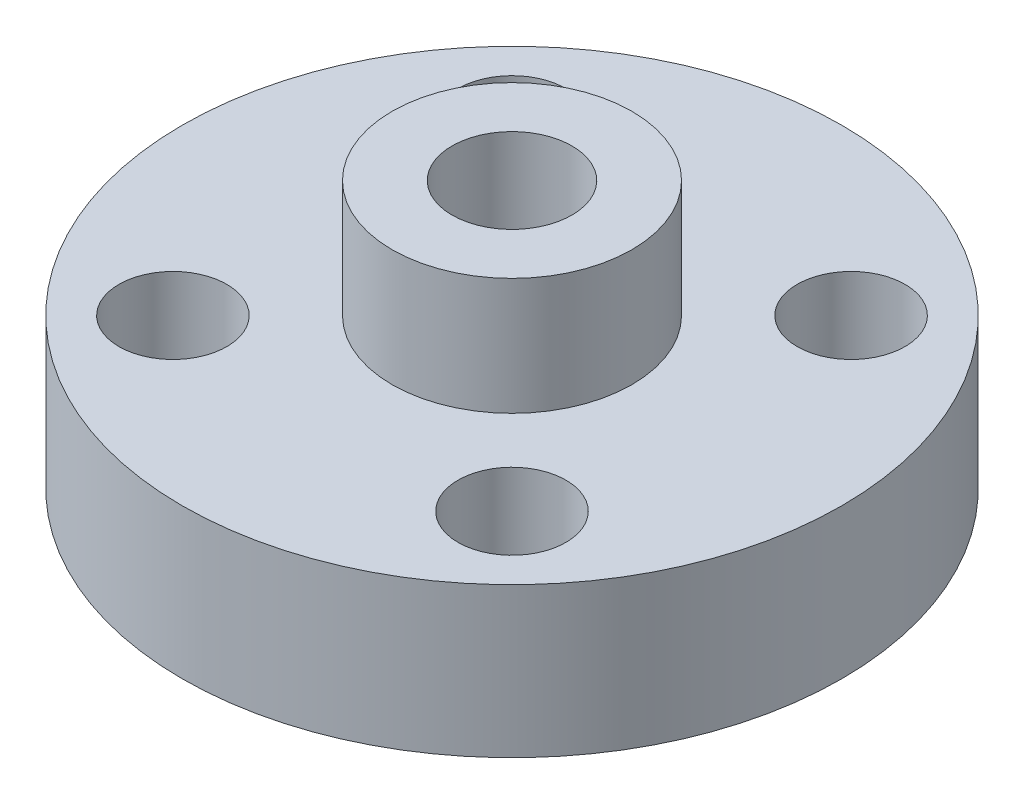
SolidWorks part; units mm, degrees
ref_plane "Front Plane" through (0, 0, 0) normal (0, 0, 1) x (1, 0, 0)
ref_plane "Top Plane" through (0, 0, 0) normal (0, 1, 0) x (1, 0, 0)
ref_plane "Right Plane" through (0, 0, 0) normal (1, 0, 0) x (0, 0, -1)
sketch "스케치1" plane through (0, 0, 0) normal (0, 1, 0) x (1, 0, 0)
  circle A0 centre (0, 0) radius 11
extrude "보스-돌출1" add sketch "스케치1" along normal blind 5
sketch "스케치2" plane through (0, 5, 0) normal (0, 1, 0) x (1, 0, 0)
  circle A0 centre (0, 0) radius 4
extrude "보스-돌출2" add sketch "스케치2" along normal blind 3.9
sketch "스케치3" plane through (0, 5, 0) normal (0, 1, 0) x (1, 0, 0)
  line L0 (0, 0) -> (-50000, 0) construction
  line L1 (0, 0) -> (35355.3391, 35355.3391) construction
  line L2 (0, 0) -> (35355.3391, -35355.3391) construction
  circle A0 centre (0, 0) radius 8 construction
  circle A1 centre (5.6569, 5.6569) radius 1.8
  circle A2 centre (-5.6569, -5.6569) radius 1.8
  circle A3 centre (-5.6569, 5.6569) radius 1.8
  circle A4 centre (5.6569, -5.6569) radius 1.8
extrude "컷-돌출1" cut sketch "스케치3" against normal through all
sketch "스케치4" plane through (0, 8.9, 0) normal (0, 1, 0) x (1, 0, 0)
  circle A0 centre (0, 0) radius 2
extrude "컷-돌출2" cut sketch "스케치4" against normal through all
